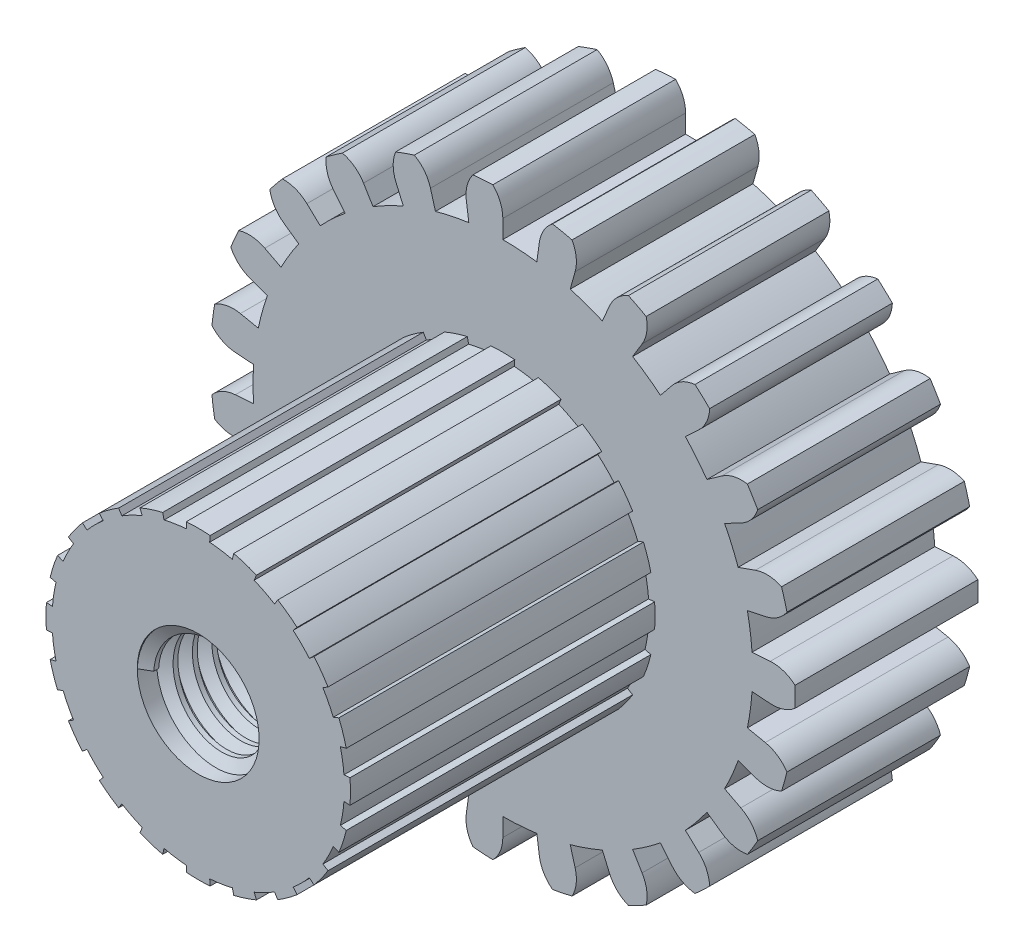
SolidWorks part; units mm, degrees
ref_plane "Front Plane" through (0, 0, 0) normal (0, 0, 1) x (1, 0, 0)
ref_plane "Top Plane" through (0, 0, 0) normal (0, 1, 0) x (1, 0, 0)
ref_plane "Right Plane" through (0, 0, 0) normal (1, 0, 0) x (0, 0, -1)
sketch "Sketch1" plane through (0, 0, 0) normal (0, 0, 1) x (1, 0, 0)
  line L0 (0, 0) -> (4.8, 0) construction
  line L1 (0, 0) -> (4.0618, 0.5583) construction
  line L2 (0, 0) -> (4.7888, 0.3276) construction
  line L3 (0, 0) -> (4.7972, 0.1639) construction
  line L4 (4.0904, 0.2798) -> (4.3897, 0.3003)
  line L5 (4.0904, -0.2798) -> (4.3897, -0.3003)
  line L6 (4.0142, -0.8342) -> (4.308, -0.8952)
  line L7 (3.8633, -1.373) -> (4.1459, -1.4735)
  line L8 (3.6403, -1.8863) -> (3.9067, -2.0243)
  line L9 (3.3496, -2.3644) -> (3.5947, -2.5374)
  line L10 (2.9964, -2.7985) -> (3.2157, -3.0032)
  line L11 (2.5875, -3.1804) -> (2.7768, -3.4131)
  line L12 (2.1303, -3.5031) -> (2.2862, -3.7594)
  line L13 (1.6334, -3.7606) -> (1.753, -4.0357)
  line L14 (1.1062, -3.948) -> (1.1871, -4.2368)
  line L15 (0.5583, -4.0618) -> (0.5991, -4.359)
  line L16 (0, -4.1) -> (0, -4.4)
  line L17 (-0.5583, -4.0618) -> (-0.5991, -4.359)
  line L18 (-1.1062, -3.948) -> (-1.1871, -4.2368)
  line L19 (-1.6334, -3.7606) -> (-1.753, -4.0357)
  line L20 (-2.1303, -3.5031) -> (-2.2862, -3.7594)
  line L21 (-2.5875, -3.1804) -> (-2.7768, -3.4131)
  line L22 (-2.9964, -2.7985) -> (-3.2157, -3.0032)
  line L23 (-3.3496, -2.3644) -> (-3.5947, -2.5374)
  line L24 (-3.6403, -1.8863) -> (-3.9067, -2.0243)
  line L25 (-3.8633, -1.373) -> (-4.1459, -1.4735)
  line L26 (-4.0142, -0.8342) -> (-4.308, -0.8952)
  line L27 (-4.0904, -0.2798) -> (-4.3897, -0.3003)
  line L28 (-4.0904, 0.2798) -> (-4.3897, 0.3003)
  line L29 (-4.0142, 0.8342) -> (-4.308, 0.8952)
  line L30 (-3.8633, 1.373) -> (-4.1459, 1.4735)
  line L31 (-3.6403, 1.8863) -> (-3.9067, 2.0243)
  line L32 (-3.3496, 2.3644) -> (-3.5947, 2.5374)
  line L33 (-2.9964, 2.7985) -> (-3.2157, 3.0032)
  line L34 (-2.5875, 3.1804) -> (-2.7768, 3.4131)
  line L35 (-2.1303, 3.5031) -> (-2.2862, 3.7594)
  line L36 (-1.6334, 3.7606) -> (-1.753, 4.0357)
  line L37 (-1.1062, 3.948) -> (-1.1871, 4.2368)
  line L38 (-0.5583, 4.0618) -> (-0.5991, 4.359)
  line L39 (0, 4.1) -> (0, 4.4)
  line L40 (0.5583, 4.0618) -> (0.5991, 4.359)
  line L41 (1.1062, 3.948) -> (1.1871, 4.2368)
  line L42 (1.6334, 3.7606) -> (1.753, 4.0357)
  line L43 (2.1303, 3.5031) -> (2.2862, 3.7594)
  line L44 (2.5875, 3.1804) -> (2.7768, 3.4131)
  line L45 (2.9964, 2.7985) -> (3.2157, 3.0032)
  line L46 (3.3496, 2.3644) -> (3.5947, 2.5374)
  line L47 (3.6403, 1.8863) -> (3.9067, 2.0243)
  line L48 (3.8633, 1.373) -> (4.1459, 1.4735)
  line L49 (4.0142, 0.8342) -> (4.308, 0.8952)
  arc A0 (4.8, 0) -> (4.7938, -0.2435) centre (0, 0) ccw construction
  circle A1 centre (0, 0) radius 4.4 construction
  circle A2 centre (0, 0) radius 4.1 construction
  arc A3 (4.0618, 0.5583) -> (4.0904, 0.2798) centre (0, 0) cw
  arc A4 (4.7972, 0.1639) -> (4.3897, 0.3003) centre (4.4282, -0.2617) ccw
  arc A5 (4.7972, 0.1639) -> (4.7972, -0.1639) centre (0, 0) cw
  arc A6 (4.7972, -0.1639) -> (4.3897, -0.3003) centre (4.4282, 0.2617) cw
  arc A7 (4.0618, -0.5583) -> (4.0904, -0.2798) centre (0, 0) ccw
  arc A8 (4.0618, -0.5583) -> (4.0142, -0.8342) centre (0, 0) cw
  arc A9 (4.6635, -1.1365) -> (4.308, -0.8952) centre (4.1934, -1.4467) ccw
  arc A10 (4.6635, -1.1365) -> (4.5751, -1.4521) centre (0, 0) cw
  arc A11 (4.5751, -1.4521) -> (4.1459, -1.4735) centre (4.3346, -0.9427) cw
  arc A12 (3.7606, -1.6334) -> (3.8633, -1.373) centre (0, 0) ccw
  arc A13 (3.7606, -1.6334) -> (3.6403, -1.8863) centre (0, 0) cw
  arc A14 (4.184, -2.3525) -> (3.9067, -2.0243) centre (3.6475, -2.5244) ccw
  arc A15 (4.184, -2.3525) -> (4.0137, -2.6326) centre (0, 0) cw
  arc A16 (4.0137, -2.6326) -> (3.5947, -2.5374) centre (3.9195, -2.0772) cw
  arc A17 (3.1804, -2.5875) -> (3.3496, -2.3644) centre (0, 0) ccw
  arc A18 (3.1804, -2.5875) -> (2.9964, -2.7985) centre (0, 0) cw
  arc A19 (3.3941, -3.3941) -> (3.2157, -3.0032) centre (2.8312, -3.4149) ccw
  arc A20 (3.3941, -3.3941) -> (3.1546, -3.6178) centre (0, 0) cw
  arc A21 (3.1546, -3.6178) -> (2.7768, -3.4131) centre (3.2138, -3.0576) cw
  arc A22 (2.3644, -3.3496) -> (2.5875, -3.1804) centre (0, 0) ccw
  arc A23 (2.3644, -3.3496) -> (2.1303, -3.5031) centre (0, 0) cw
  arc A24 (2.3525, -4.184) -> (2.2862, -3.7594) centre (1.8049, -4.0521) ccw
  arc A25 (2.3525, -4.184) -> (2.0615, -4.3348) centre (0, 0) cw
  arc A26 (2.0615, -4.3348) -> (1.753, -4.0357) centre (2.2696, -3.8113) cw
  arc A27 (1.373, -3.8633) -> (1.6334, -3.7606) centre (0, 0) ccw
  arc A28 (1.373, -3.8633) -> (1.1062, -3.948) centre (0, 0) cw
  arc A29 (1.1365, -4.6635) -> (1.1871, -4.2368) centre (0.6447, -4.3888) ccw
  arc A30 (1.1365, -4.6635) -> (0.8156, -4.7302) centre (0, 0) cw
  arc A31 (0.8156, -4.7302) -> (0.5991, -4.359) centre (1.1572, -4.2823) cw
  arc A32 (0.2798, -4.0904) -> (0.5583, -4.0618) centre (0, 0) ccw
  arc A33 (0.2798, -4.0904) -> (0, -4.1) centre (0, 0) cw
  arc A34 (-0.1639, -4.7972) -> (0, -4.4) centre (-0.5633, -4.4) ccw
  arc A35 (-0.1639, -4.7972) -> (-0.4909, -4.7748) centre (0, 0) cw
  arc A36 (-0.4909, -4.7748) -> (-0.5991, -4.359) centre (-0.0411, -4.4357) cw
  arc A37 (-0.8342, -4.0142) -> (-0.5583, -4.0618) centre (0, 0) ccw
  arc A38 (-0.8342, -4.0142) -> (-1.1062, -3.948) centre (0, 0) cw
  arc A39 (-1.4521, -4.5751) -> (-1.1871, -4.2368) centre (-1.7295, -4.0849) ccw
  arc A40 (-1.4521, -4.5751) -> (-1.7609, -4.4653) centre (0, 0) cw
  arc A41 (-1.7609, -4.4653) -> (-1.753, -4.0357) centre (-1.2363, -4.2602) cw
  arc A42 (-1.8863, -3.6403) -> (-1.6334, -3.7606) centre (0, 0) ccw
  arc A43 (-1.8863, -3.6403) -> (-2.1303, -3.5031) centre (0, 0) cw
  arc A44 (-2.6326, -4.0137) -> (-2.2862, -3.7594) centre (-2.7675, -3.4668) ccw
  arc A45 (-2.6326, -4.0137) -> (-2.9003, -3.8247) centre (0, 0) cw
  arc A46 (-2.9003, -3.8247) -> (-2.7768, -3.4131) centre (-2.3398, -3.7686) cw
  arc A47 (-2.7985, -2.9964) -> (-2.5875, -3.1804) centre (0, 0) ccw
  arc A48 (-2.7985, -2.9964) -> (-2.9964, -2.7985) centre (0, 0) cw
  arc A49 (-3.6178, -3.1546) -> (-3.2157, -3.0032) centre (-3.6002, -2.5915) ccw
  arc A50 (-3.6178, -3.1546) -> (-3.8247, -2.9003) centre (0, 0) cw
  arc A51 (-3.8247, -2.9003) -> (-3.5947, -2.5374) centre (-3.2698, -2.9976) cw
  arc A52 (-3.5031, -2.1303) -> (-3.3496, -2.3644) centre (0, 0) ccw
  arc A53 (-3.5031, -2.1303) -> (-3.6403, -1.8863) centre (0, 0) cw
  arc A54 (-4.3348, -2.0615) -> (-3.9067, -2.0243) centre (-4.1659, -1.5241) ccw
  arc A55 (-4.3348, -2.0615) -> (-4.4653, -1.7609) centre (0, 0) cw
  arc A56 (-4.4653, -1.7609) -> (-4.1459, -1.4735) centre (-3.9573, -2.0043) cw
  arc A57 (-3.948, -1.1062) -> (-3.8633, -1.373) centre (0, 0) ccw
  arc A58 (-3.948, -1.1062) -> (-4.0142, -0.8342) centre (0, 0) cw
  arc A59 (-4.7302, -0.8156) -> (-4.308, -0.8952) centre (-4.4226, -0.3437) ccw
  arc A60 (-4.7302, -0.8156) -> (-4.7748, -0.4909) centre (0, 0) cw
  arc A61 (-4.7748, -0.4909) -> (-4.3897, -0.3003) centre (-4.3513, -0.8623) cw
  arc A62 (-4.1, 0) -> (-4.0904, -0.2798) centre (0, 0) ccw
  arc A63 (-4.1, 0) -> (-4.0904, 0.2798) centre (0, 0) cw
  arc A64 (-4.7748, 0.4909) -> (-4.3897, 0.3003) centre (-4.3513, 0.8623) ccw
  arc A65 (-4.7748, 0.4909) -> (-4.7302, 0.8156) centre (0, 0) cw
  arc A66 (-4.7302, 0.8156) -> (-4.308, 0.8952) centre (-4.4226, 0.3437) cw
  arc A67 (-3.948, 1.1062) -> (-4.0142, 0.8342) centre (0, 0) ccw
  arc A68 (-3.948, 1.1062) -> (-3.8633, 1.373) centre (0, 0) cw
  arc A69 (-4.4653, 1.7609) -> (-4.1459, 1.4735) centre (-3.9573, 2.0043) ccw
  arc A70 (-4.4653, 1.7609) -> (-4.3348, 2.0615) centre (0, 0) cw
  arc A71 (-4.3348, 2.0615) -> (-3.9067, 2.0243) centre (-4.1659, 1.5241) cw
  arc A72 (-3.5031, 2.1303) -> (-3.6403, 1.8863) centre (0, 0) ccw
  arc A73 (-3.5031, 2.1303) -> (-3.3496, 2.3644) centre (0, 0) cw
  arc A74 (-3.8247, 2.9003) -> (-3.5947, 2.5374) centre (-3.2698, 2.9976) ccw
  arc A75 (-3.8247, 2.9003) -> (-3.6178, 3.1546) centre (0, 0) cw
  arc A76 (-3.6178, 3.1546) -> (-3.2157, 3.0032) centre (-3.6002, 2.5915) cw
  arc A77 (-2.7985, 2.9964) -> (-2.9964, 2.7985) centre (0, 0) ccw
  arc A78 (-2.7985, 2.9964) -> (-2.5875, 3.1804) centre (0, 0) cw
  arc A79 (-2.9003, 3.8247) -> (-2.7768, 3.4131) centre (-2.3398, 3.7686) ccw
  arc A80 (-2.9003, 3.8247) -> (-2.6326, 4.0137) centre (0, 0) cw
  arc A81 (-2.6326, 4.0137) -> (-2.2862, 3.7594) centre (-2.7675, 3.4668) cw
  arc A82 (-1.8863, 3.6403) -> (-2.1303, 3.5031) centre (0, 0) ccw
  arc A83 (-1.8863, 3.6403) -> (-1.6334, 3.7606) centre (0, 0) cw
  arc A84 (-1.7609, 4.4653) -> (-1.753, 4.0357) centre (-1.2363, 4.2602) ccw
  arc A85 (-1.7609, 4.4653) -> (-1.4521, 4.5751) centre (0, 0) cw
  arc A86 (-1.4521, 4.5751) -> (-1.1871, 4.2368) centre (-1.7295, 4.0849) cw
  arc A87 (-0.8342, 4.0142) -> (-1.1062, 3.948) centre (0, 0) ccw
  arc A88 (-0.8342, 4.0142) -> (-0.5583, 4.0618) centre (0, 0) cw
  arc A89 (-0.4909, 4.7748) -> (-0.5991, 4.359) centre (-0.0411, 4.4357) ccw
  arc A90 (-0.4909, 4.7748) -> (-0.1639, 4.7972) centre (0, 0) cw
  arc A91 (-0.1639, 4.7972) -> (0, 4.4) centre (-0.5633, 4.4) cw
  arc A92 (0.2798, 4.0904) -> (0, 4.1) centre (0, 0) ccw
  arc A93 (0.2798, 4.0904) -> (0.5583, 4.0618) centre (0, 0) cw
  arc A94 (0.8156, 4.7302) -> (0.5991, 4.359) centre (1.1572, 4.2823) ccw
  arc A95 (0.8156, 4.7302) -> (1.1365, 4.6635) centre (0, 0) cw
  arc A96 (1.1365, 4.6635) -> (1.1871, 4.2368) centre (0.6447, 4.3888) cw
  arc A97 (1.373, 3.8633) -> (1.1062, 3.948) centre (0, 0) ccw
  arc A98 (1.373, 3.8633) -> (1.6334, 3.7606) centre (0, 0) cw
  arc A99 (2.0615, 4.3348) -> (1.753, 4.0357) centre (2.2696, 3.8113) ccw
  arc A100 (2.0615, 4.3348) -> (2.3525, 4.184) centre (0, 0) cw
  arc A101 (2.3525, 4.184) -> (2.2862, 3.7594) centre (1.8049, 4.0521) cw
  arc A102 (2.3644, 3.3496) -> (2.1303, 3.5031) centre (0, 0) ccw
  arc A103 (2.3644, 3.3496) -> (2.5875, 3.1804) centre (0, 0) cw
  arc A104 (3.1546, 3.6178) -> (2.7768, 3.4131) centre (3.2138, 3.0576) ccw
  arc A105 (3.1546, 3.6178) -> (3.3941, 3.3941) centre (0, 0) cw
  arc A106 (3.3941, 3.3941) -> (3.2157, 3.0032) centre (2.8312, 3.4149) cw
  arc A107 (3.1804, 2.5875) -> (2.9964, 2.7985) centre (0, 0) ccw
  arc A108 (3.1804, 2.5875) -> (3.3496, 2.3644) centre (0, 0) cw
  arc A109 (4.0137, 2.6326) -> (3.5947, 2.5374) centre (3.9195, 2.0772) ccw
  arc A110 (4.0137, 2.6326) -> (4.184, 2.3525) centre (0, 0) cw
  arc A111 (4.184, 2.3525) -> (3.9067, 2.0243) centre (3.6475, 2.5244) cw
  arc A112 (3.7606, 1.6334) -> (3.6403, 1.8863) centre (0, 0) ccw
  arc A113 (3.7606, 1.6334) -> (3.8633, 1.373) centre (0, 0) cw
  arc A114 (4.5751, 1.4521) -> (4.1459, 1.4735) centre (4.3346, 0.9427) ccw
  arc A115 (4.5751, 1.4521) -> (4.6635, 1.1365) centre (0, 0) cw
  arc A116 (4.6635, 1.1365) -> (4.308, 0.8952) centre (4.1934, 1.4467) cw
  arc A117 (4.0618, 0.5583) -> (4.0142, 0.8342) centre (0, 0) ccw
  point P241 (0, 0)
  dimension "D1" = 9.6
  dimension "D2" = 0.7
  dimension "D3" = 8.8
  dimension "D4" = 7.826
  dimension "D5" = 3.913
  dimension "D6" = 1.957
  dimension "D7" = 23
extrude "Boss-Extrude1" add sketch "Sketch1" along normal blind 3 contours A3 A117 L49 A116 A115 A114 L48 A113 A112 L47 A111 A110 A109 L46 A108 A107 L45 A106 A105 A104 L44 A103 A102 L43 A101 A100 A99 L42 A98 A97 L41 A96 A95 A94 L40 A93 A92 L39 A91 A90 A89 L38 A88 A87 L37 A86 A85 A84 L36 A83 A82 region at (0, 0, 0)
sketch "Sketch2" plane through (0, 0, 3) normal (0, 0, 1) x (1, 0, 0)
  line L0 (0, 0) -> (2.8072, 0) construction
  line L1 (0, 0) -> (2.7718, 0.439) construction
  line L2 (0, 0) -> (2.8476, 0.2241) construction
  line L3 (2.3926, 0.1883) -> (2.4914, 0.1961)
  line L4 (2.3926, -0.1883) -> (2.4914, -0.1961)
  line L5 (2.3337, -0.5603) -> (2.4301, -0.5834)
  line L6 (2.2173, -0.9184) -> (2.3089, -0.9564)
  line L7 (2.0463, -1.254) -> (2.1309, -1.3058)
  line L8 (1.825, -1.5587) -> (1.9004, -1.6231)
  line L9 (1.5587, -1.825) -> (1.6231, -1.9004)
  line L10 (1.254, -2.0463) -> (1.3058, -2.1309)
  line L11 (0.9184, -2.2173) -> (0.9564, -2.3089)
  line L12 (0.5603, -2.3337) -> (0.5834, -2.4301)
  line L13 (0.1883, -2.3926) -> (0.1961, -2.4914)
  line L14 (-0.1883, -2.3926) -> (-0.1961, -2.4914)
  line L15 (-0.5603, -2.3337) -> (-0.5834, -2.4301)
  line L16 (-0.9184, -2.2173) -> (-0.9564, -2.3089)
  line L17 (-1.254, -2.0463) -> (-1.3058, -2.1309)
  line L18 (-1.5587, -1.825) -> (-1.6231, -1.9004)
  line L19 (-1.825, -1.5587) -> (-1.9004, -1.6231)
  line L20 (-2.0463, -1.254) -> (-2.1309, -1.3058)
  line L21 (-2.2173, -0.9184) -> (-2.3089, -0.9564)
  line L22 (-2.3337, -0.5603) -> (-2.4301, -0.5834)
  line L23 (-2.3926, -0.1883) -> (-2.4914, -0.1961)
  line L24 (-2.3926, 0.1883) -> (-2.4914, 0.1961)
  line L25 (-2.3337, 0.5603) -> (-2.4301, 0.5834)
  line L26 (-2.2173, 0.9184) -> (-2.3089, 0.9564)
  line L27 (-2.0463, 1.254) -> (-2.1309, 1.3058)
  line L28 (-1.825, 1.5587) -> (-1.9004, 1.6231)
  line L29 (-1.5587, 1.825) -> (-1.6231, 1.9004)
  line L30 (-1.254, 2.0463) -> (-1.3058, 2.1309)
  line L31 (-0.9184, 2.2173) -> (-0.9564, 2.3089)
  line L32 (-0.5603, 2.3337) -> (-0.5834, 2.4301)
  line L33 (-0.1883, 2.3926) -> (-0.1961, 2.4914)
  line L34 (0.1883, 2.3926) -> (0.1961, 2.4914)
  line L35 (0.5603, 2.3337) -> (0.5834, 2.4301)
  line L36 (0.9184, 2.2173) -> (0.9564, 2.3089)
  line L37 (1.254, 2.0463) -> (1.3058, 2.1309)
  line L38 (1.5587, 1.825) -> (1.6231, 1.9004)
  line L39 (1.825, 1.5587) -> (1.9004, 1.6231)
  line L40 (2.0463, 1.254) -> (2.1309, 1.3058)
  line L41 (2.2173, 0.9184) -> (2.3089, 0.9564)
  line L42 (2.3337, 0.5603) -> (2.4301, 0.5834)
  circle A0 centre (0, 0) radius 2.5 construction
  circle A1 centre (0, 0) radius 1
  circle A2 centre (0, 0) radius 2.4 construction
  arc A3 (2.3926, 0.1883) -> (2.3705, 0.3754) centre (0, 0) ccw
  arc A4 (2.4914, 0.1961) -> (2.4914, -0.1961) centre (0, 0) cw
  arc A5 (2.3926, -0.1883) -> (2.3705, -0.3754) centre (0, 0) cw
  arc A6 (2.3337, -0.5603) -> (2.3705, -0.3754) centre (0, 0) ccw
  arc A7 (2.2173, -0.9184) -> (2.1384, -1.0896) centre (0, 0) cw
  arc A8 (2.4301, -0.5834) -> (2.3089, -0.9564) centre (0, 0) cw
  arc A9 (2.0463, -1.254) -> (2.1384, -1.0896) centre (0, 0) ccw
  arc A10 (1.825, -1.5587) -> (1.6971, -1.6971) centre (0, 0) cw
  arc A11 (2.1309, -1.3058) -> (1.9004, -1.6231) centre (0, 0) cw
  arc A12 (1.5587, -1.825) -> (1.6971, -1.6971) centre (0, 0) ccw
  arc A13 (1.254, -2.0463) -> (1.0896, -2.1384) centre (0, 0) cw
  arc A14 (1.6231, -1.9004) -> (1.3058, -2.1309) centre (0, 0) cw
  arc A15 (0.9184, -2.2173) -> (1.0896, -2.1384) centre (0, 0) ccw
  arc A16 (0.5603, -2.3337) -> (0.3754, -2.3705) centre (0, 0) cw
  arc A17 (0.9564, -2.3089) -> (0.5834, -2.4301) centre (0, 0) cw
  arc A18 (0.1883, -2.3926) -> (0.3754, -2.3705) centre (0, 0) ccw
  arc A19 (-0.1883, -2.3926) -> (-0.3754, -2.3705) centre (0, 0) cw
  arc A20 (0.1961, -2.4914) -> (-0.1961, -2.4914) centre (0, 0) cw
  arc A21 (-0.5603, -2.3337) -> (-0.3754, -2.3705) centre (0, 0) ccw
  arc A22 (-0.9184, -2.2173) -> (-1.0896, -2.1384) centre (0, 0) cw
  arc A23 (-0.5834, -2.4301) -> (-0.9564, -2.3089) centre (0, 0) cw
  arc A24 (-1.254, -2.0463) -> (-1.0896, -2.1384) centre (0, 0) ccw
  arc A25 (-1.5587, -1.825) -> (-1.6971, -1.6971) centre (0, 0) cw
  arc A26 (-1.3058, -2.1309) -> (-1.6231, -1.9004) centre (0, 0) cw
  arc A27 (-1.825, -1.5587) -> (-1.6971, -1.6971) centre (0, 0) ccw
  arc A28 (-2.0463, -1.254) -> (-2.1384, -1.0896) centre (0, 0) cw
  arc A29 (-1.9004, -1.6231) -> (-2.1309, -1.3058) centre (0, 0) cw
  arc A30 (-2.2173, -0.9184) -> (-2.1384, -1.0896) centre (0, 0) ccw
  arc A31 (-2.3337, -0.5603) -> (-2.3705, -0.3754) centre (0, 0) cw
  arc A32 (-2.3089, -0.9564) -> (-2.4301, -0.5834) centre (0, 0) cw
  arc A33 (-2.3926, -0.1883) -> (-2.3705, -0.3754) centre (0, 0) ccw
  arc A34 (-2.3926, 0.1883) -> (-2.3705, 0.3754) centre (0, 0) cw
  arc A35 (-2.4914, -0.1961) -> (-2.4914, 0.1961) centre (0, 0) cw
  arc A36 (-2.3337, 0.5603) -> (-2.3705, 0.3754) centre (0, 0) ccw
  arc A37 (-2.2173, 0.9184) -> (-2.1384, 1.0896) centre (0, 0) cw
  arc A38 (-2.4301, 0.5834) -> (-2.3089, 0.9564) centre (0, 0) cw
  arc A39 (-2.0463, 1.254) -> (-2.1384, 1.0896) centre (0, 0) ccw
  arc A40 (-1.825, 1.5587) -> (-1.6971, 1.6971) centre (0, 0) cw
  arc A41 (-2.1309, 1.3058) -> (-1.9004, 1.6231) centre (0, 0) cw
  arc A42 (-1.5587, 1.825) -> (-1.6971, 1.6971) centre (0, 0) ccw
  arc A43 (-1.254, 2.0463) -> (-1.0896, 2.1384) centre (0, 0) cw
  arc A44 (-1.6231, 1.9004) -> (-1.3058, 2.1309) centre (0, 0) cw
  arc A45 (-0.9184, 2.2173) -> (-1.0896, 2.1384) centre (0, 0) ccw
  arc A46 (-0.5603, 2.3337) -> (-0.3754, 2.3705) centre (0, 0) cw
  arc A47 (-0.9564, 2.3089) -> (-0.5834, 2.4301) centre (0, 0) cw
  arc A48 (-0.1883, 2.3926) -> (-0.3754, 2.3705) centre (0, 0) ccw
  arc A49 (0.1883, 2.3926) -> (0.3754, 2.3705) centre (0, 0) cw
  arc A50 (-0.1961, 2.4914) -> (0.1961, 2.4914) centre (0, 0) cw
  arc A51 (0.5603, 2.3337) -> (0.3754, 2.3705) centre (0, 0) ccw
  arc A52 (0.9184, 2.2173) -> (1.0896, 2.1384) centre (0, 0) cw
  arc A53 (0.5834, 2.4301) -> (0.9564, 2.3089) centre (0, 0) cw
  arc A54 (1.254, 2.0463) -> (1.0896, 2.1384) centre (0, 0) ccw
  arc A55 (1.5587, 1.825) -> (1.6971, 1.6971) centre (0, 0) cw
  arc A56 (1.3058, 2.1309) -> (1.6231, 1.9004) centre (0, 0) cw
  arc A57 (1.825, 1.5587) -> (1.6971, 1.6971) centre (0, 0) ccw
  arc A58 (2.0463, 1.254) -> (2.1384, 1.0896) centre (0, 0) cw
  arc A59 (1.9004, 1.6231) -> (2.1309, 1.3058) centre (0, 0) cw
  arc A60 (2.2173, 0.9184) -> (2.1384, 1.0896) centre (0, 0) ccw
  arc A61 (2.3337, 0.5603) -> (2.3705, 0.3754) centre (0, 0) cw
  arc A62 (2.3089, 0.9564) -> (2.4301, 0.5834) centre (0, 0) cw
  point P131 (0, 0)
  dimension "D1" = 5
  dimension "D2" = 2
  dimension "D3" = 4.8
  dimension "D4" = 9
  dimension "D5" = 4.5
  dimension "D6" = 20
extrude "Boss-Extrude2" add sketch "Sketch2" along normal blind 5 contours A62 L41 A60 A58 L40 A59 L39 A57 A55 L38 A56 L37 A54 A52 L36 A53 L35 A51 A49 L34 A50 L33 A48 A46 L32 A47 L31 A45 A43 L30 A44 L29 A42 A40 L28 A41 L27 A39 A37 L26 A38 L25 A36 A34 L24 A35 L23 A33 A31 L22 A32 region at (2.4476, 0.1217, 3)
thread "Thread1" pitch 0.3175 method extrude profile "Thread Profile1" start angle 0, offset 0, length 0, pitch 0.3175, diameter 2
ref_plane "Plane1" through (-1, 0, 8) normal (0, -1, 0) x (-1, 0, 0)
sketch "Thread Profile1" plane through (-1, 0, 8) normal (0, -1, 0) x (-1, 0, 0)
  line L0 (0, 0) -> (0, 0.3175) construction
  line L11 (0, 0) -> (0, 0.2778)
  line L12 (0, 0.2778) -> (-0.1719, 0.1786)
  line L13 (-0.1719, 0.1786) -> (-0.1719, 0.0992)
  line L15 (-0.1719, 0.0992) -> (0, 0)
  line L17 (-0.1719, 0.1389) -> (0, 0.1389) construction
  point P2 (0, 0)
  dimension "Pitch" = 0.3175
  dimension "Profile_Angle" = 60
  dimension "Profile_Land" = 0.0794
  dimension "Profile_Height" = 0.1719
sketch "Sketch5" plane through (0, 0, 0) normal (0, 0, -1) x (-1, 0, 0)
  line L0 (0.35, 0.5477) -> (0.35, -0.5477)
  arc A0 (0.35, 0.5477) -> (0.35, -0.5477) centre (0, 0) ccw
  dimension "D1" = 1.3
  dimension "D2" = 0.35
extrude "Cut-Extrude1" cut sketch "Sketch5" against normal blind 3
